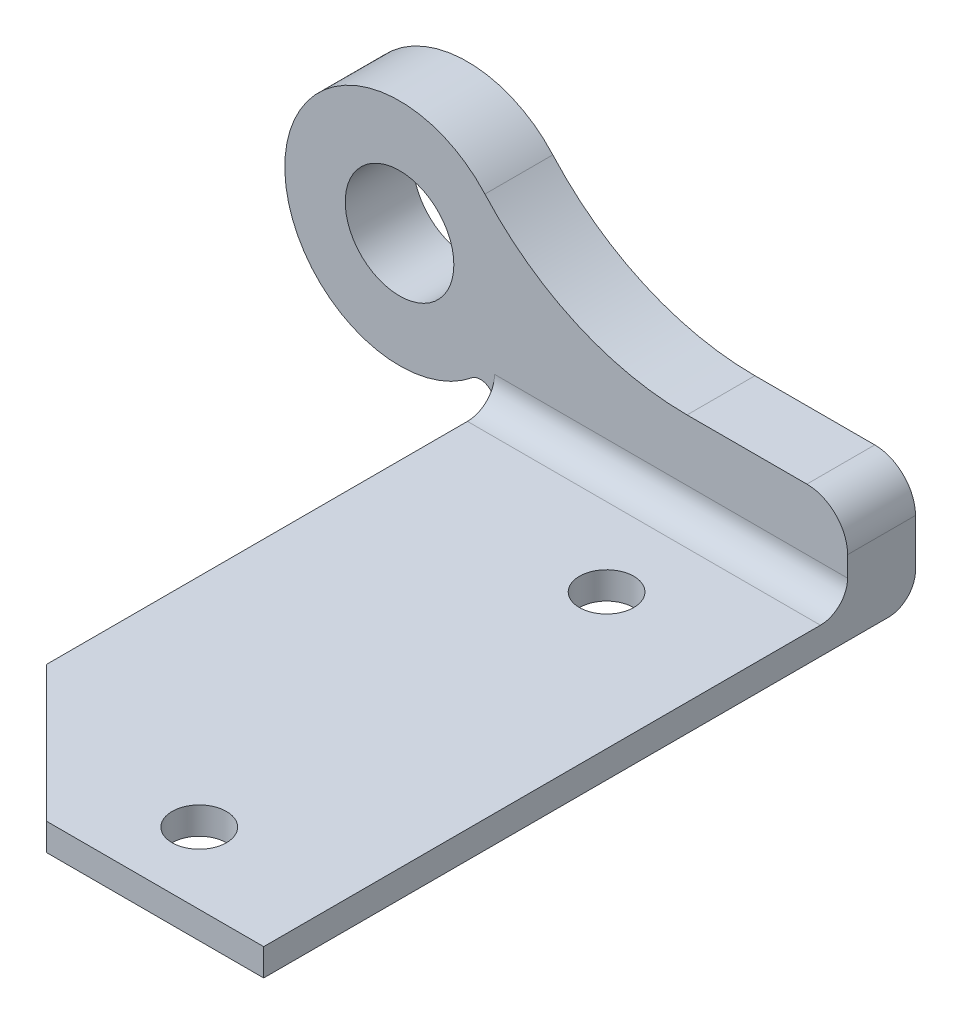
SolidWorks part; units mm, degrees
material "6061 合金"
ref_plane "前视基准面" through (0, 0, 0) normal (0, 0, 1) x (1, 0, 0)
ref_plane "上视基准面" through (0, 0, 0) normal (0, 1, 0) x (1, 0, 0)
ref_plane "右视基准面" through (0, 0, 0) normal (1, 0, 0) x (0, 0, -1)
sketch "草图1" plane through (0, 0, 0) normal (0, 0, 1) x (1, 0, 0)
  line L0 (-5.4584, -21.0602) -> (-5.4584, -21.2593)
  line L1 (-5.4584, -21.2593) -> (20.5416, -21.2593)
  line L2 (20.5416, -21.2593) -> (20.5416, -17.7593)
  line L3 (17.5416, -14.7593) -> (8.7172, -14.7593)
  line L4 (20.5416, -21.2593) -> (20.5416, -23.2593)
  line L5 (18.5416, -23.2593) -> (-3.4584, -23.2593)
  line L6 (-5.4584, -23.2593) -> (-3.4584, -23.2593)
  line L7 (-5.4584, -21.2593) -> (-5.4584, -23.2593)
  line L8 (18.5416, -23.2593) -> (20.5416, -23.2593)
  arc A0 (-5.4584, -21.0602) -> (-7.0933, -20.2876) centre (-6.4982, -21.1445) ccw
  arc A1 (20.5416, -17.7593) -> (17.5416, -14.7593) centre (17.5416, -17.7593) ccw
  arc A2 (-6.169, -8.1161) -> (8.7172, -14.7593) centre (8.7172, 5.2407) ccw
  arc A3 (-6.169, -8.1161) -> (-7.0933, -20.2876) centre (-12.4584, -13.7593) ccw
  arc A4 (-12.4584, -9.7593) -> (-12.4584, -17.7593) centre (-12.4584, -13.7593) ccw
  arc A5 (-12.4584, -17.7593) -> (-12.4584, -9.7593) centre (-12.4584, -13.7593) ccw
extrude "凸台-拉伸1" add sketch "草图1" along normal blind 3 and the other way blind 2 contours A2 A3 A0 L0 L1 L2 A1 L3 A5 A4 | L5 L8 L4 L1 L7 L6 region at (-2.6379, -15.72, 0) region at (7.5416, -22.2593, 0)
sketch "草图2" plane through (0, -23.2593, 0) normal (0, -1, 0) x (1, 0, 0)
  line L0 (20.5416, 46.0048) -> (-5.4584, 46)
  line L3 (20.5416, -2) -> (-5.4584, -2)
  line L4 (-5.4584, 2) -> (-5.4584, -2)
  line L5 (-5.4584, 46) -> (-5.4584, 2)
  line L6 (1.5416, 7) -> (14.5416, 7) construction
  line L9 (20.5416, -2) -> (-5.4584, -2) construction
  line L10 (20.5416, 46.0048) -> (20.5416, -2)
  line L11 (20.5416, 3) -> (20.5416, -2) construction
  circle A6 centre (10.5416, 40.7504) radius 2
  circle A7 centre (10.5416, 10.7504) radius 2
  dimension "D3" = 4
  dimension "D4" = 4
  dimension "D1" = 26
  dimension "D2" = 9
  dimension "D5" = 13
  dimension "D6" = 7
extrude "凸台-拉伸2" add sketch "草图2" against normal blind 2
fillet "圆角1" radius 2 1 edges at (7.5416, -23.2593, -2)
chamfer "倒角1" distance 10 angle 45 1 edges at (-5.4584, -22.2593, 46) first distance on face at (-5.4584, -21.833, 13.3694)
fillet "圆角2" radius 2 1 edges at (7.5416, -21.2593, 3)
